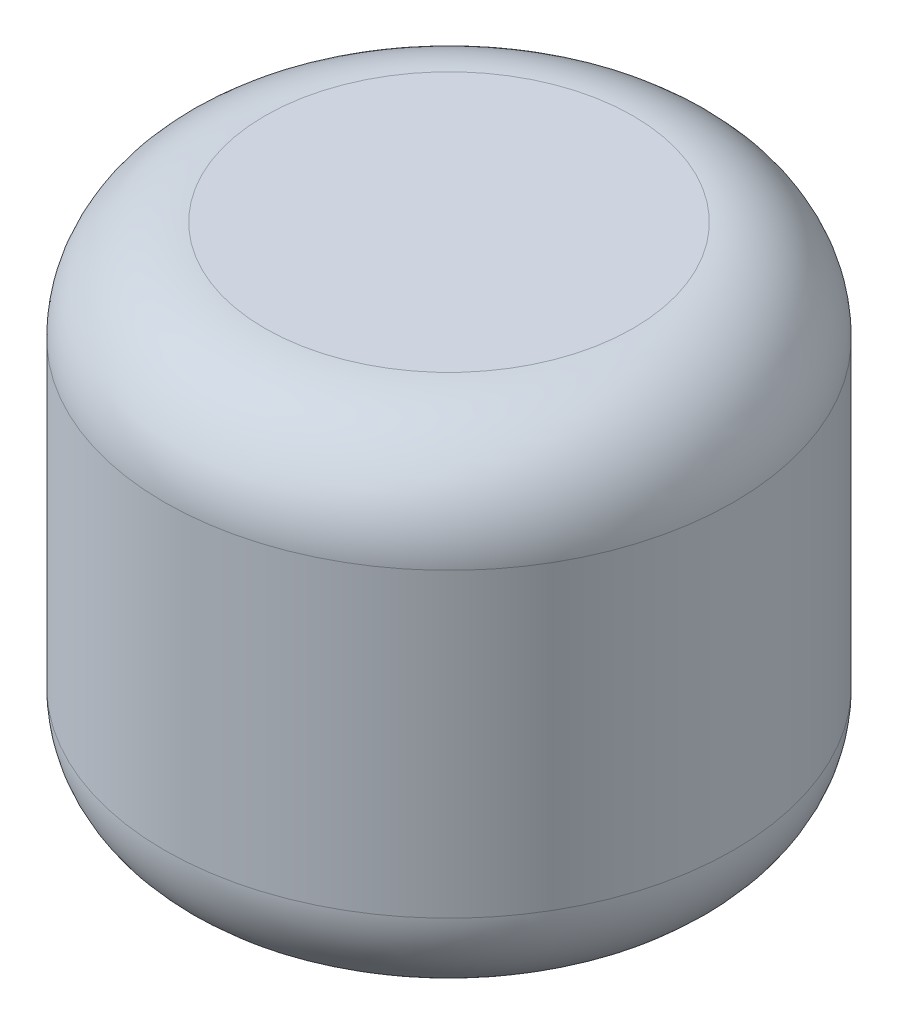
SolidWorks part; units mm, degrees
ref_plane "Спереди" through (0, 0, 0) normal (0, 0, 1) x (1, 0, 0)
ref_plane "Сверху" through (0, 0, 0) normal (0, 1, 0) x (1, 0, 0)
ref_plane "Справа" through (0, 0, 0) normal (1, 0, 0) x (0, 0, -1)
sketch "Эскиз1" plane through (0, 0, 0) normal (0, 1, 0) x (1, 0, 0)
  circle A0 centre (0, 0) radius 8.5
  dimension "D1" = 17
extrude "Бобышка-Вытянуть1" add sketch "Эскиз1" along normal blind 15
sketch "Эскиз2" plane through (0, 0, 0) normal (0, -1, 0) x (1, 0, 0)
  circle A0 centre (0, 0) radius 3
  dimension "D1" = 6
extrude "Вырез-Вытянуть1" cut sketch "Эскиз2" against normal blind 10
fillet "Скругление1" radius 3 2 edges at (0, 0, 8.5) (0, 15, 8.5)
